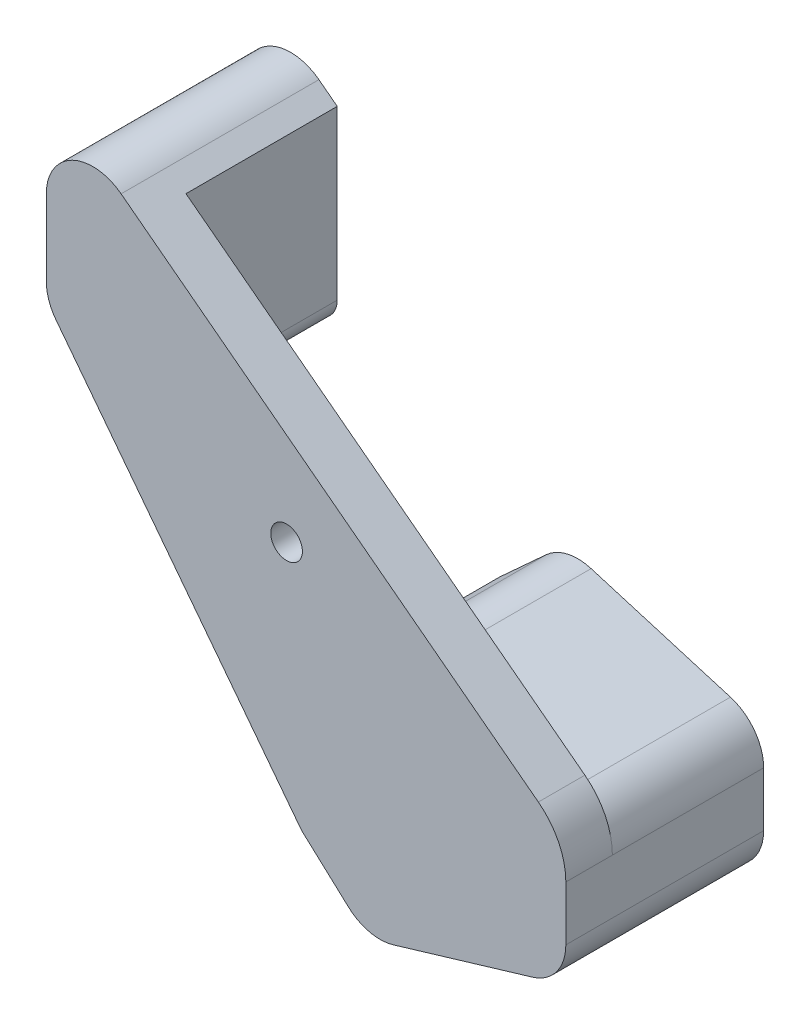
SolidWorks part; units mm, degrees
ref_plane "Front Plane" through (0, 0, 0) normal (0, 0, 1) x (1, 0, 0)
ref_plane "Top Plane" through (0, 0, 0) normal (0, 1, 0) x (1, 0, 0)
ref_plane "Right Plane" through (0, 0, 0) normal (1, 0, 0) x (0, 0, -1)
sketch "Sketch1" plane through (0, 0, 0) normal (0, 0, 1) x (1, 0, 0)
  line L0 (0, 0) -> (0, 12.7)
  line L1 (0, 12.7) -> (11.1125, 22.86)
  line L3 (11.1125, 22.86) -> (38.1, 14.7942)
  line L4 (38.1, 14.7942) -> (38.1, -19.05)
  line L5 (11.1125, 12.7) -> (11.1125, 0) construction
  line L6 (11.1125, 6.35) -> (30.1625, 6.35) construction
  line L7 (11.1125, -10.16) -> (38.1, -2.0942)
  line L8 (0, 0) -> (11.1125, -10.16)
  circle A0 centre (11.1125, 12.7) radius 2.032
  circle A1 centre (11.1125, 0) radius 2.032
  circle A2 centre (30.1625, 6.35) radius 2.032
  dimension "D3" = 4.064
  dimension "D1" = 73.36
  dimension "D2" = 38.1
  dimension "D4" = 11.1125
  dimension "D5" = 12.7
  dimension "D6" = 10.16
  dimension "D7" = 19.05
  dimension "D8" = 19.05
extrude "Boss-Extrude1" add sketch "Sketch1" along normal blind 20.6375 contours L0 L8 L7 L4 L3 L1 A2 A1 A0 region at (18.6064, 6.35, 0)
fillet "Fillet1" radius 6.35 6 edges at (38.1, 14.7942, 10.3187) (11.1125, 22.86, 10.3187) (0, 12.7, 10.3187) (38.1, -2.0942, 10.3187) (11.1125, -10.16, 10.3187) (0, 0, 10.3187)
sketch "Sketch3" plane through (0, 0, 20.6375) normal (0, 0, 1) x (1, 0, 0)
  line L0 (2.0652, -1.8882) -> (-32.7759, 43.4132)
  line L1 (-32.7759, 43.4132) -> (-32.7759, 68.8132)
  line L2 (-32.7759, 68.8132) -> (34.3497, 17.6393)
  line L6 (14.5601, -9.1296) -> (33.5684, -3.4485)
  line L7 (38.1, 2.6355) -> (38.1, 10.0645)
  line L8 (33.5684, 16.1485) -> (14.5601, 21.8296)
  line L9 (8.4569, 20.432) -> (2.0652, 14.5882)
  line L10 (0, 9.9017) -> (0, 2.7983)
  line L11 (2.0652, -1.8882) -> (8.4569, -7.732)
  line L12 (14.5601, -9.1296) -> (33.5684, -3.4485)
  line L13 (38.1, 2.6355) -> (38.1, 10.0645)
  line L17 (2.0652, -1.8882) -> (8.4569, -7.732)
  arc A0 (38.1, 10.0645) -> (34.3497, 17.6393) centre (28.575, 10.0645) ccw
  circle A1 centre (0, 31.1519) radius 2.159 construction
  circle A2 centre (0, 31.1519) radius 2.159
  arc A6 (33.5684, -3.4485) -> (38.1, 2.6355) centre (31.75, 2.6355) ccw
  arc A7 (38.1, 10.0645) -> (33.5684, 16.1485) centre (31.75, 10.0645) ccw
  arc A8 (14.5601, 21.8296) -> (8.4569, 20.432) centre (12.7417, 15.7455) ccw
  arc A9 (2.0652, 14.5882) -> (0, 9.9017) centre (6.35, 9.9017) ccw
  arc A10 (0, 2.7983) -> (2.0652, -1.8882) centre (6.35, 2.7983) ccw
  arc A11 (8.4569, -7.732) -> (14.5601, -9.1296) centre (12.7417, -3.0455) ccw
  arc A12 (33.5684, -3.4485) -> (38.1, 2.6355) centre (31.75, 2.6355) ccw
  arc A17 (8.4569, -7.732) -> (14.5601, -9.1296) centre (12.7417, -3.0455) ccw
  point P12 (34.3204, 17.9923)
  point P20 (-10.7683, 59.9009)
  point P27 (-11.5091, 59.7694)
  point P28 (-11.431, 59.8295)
  point P29 (-30.6124, 77.8528)
  point P30 (-30.6124, 84.739)
  point P31 (-32.7759, 84.3717)
  dimension "D2" = 57.15
  dimension "D3" = 9.525
  dimension "D4" = 170
  dimension "D5" = 25.4
  dimension "D1" = 0
extrude "Boss-Extrude2" add sketch "Sketch3" along normal blind 6.35
fillet "Fillet2" radius 6.35 2 edges at (-32.7759, 43.4132, 23.8125) (-32.7759, 68.8132, 23.8125)
sketch "Sketch4" plane through (0, 0, 20.6375) normal (0, 0, -1) x (-1, 0, 0)
  line L0 (32.7759, 55.9874) -> (32.7759, 45.5727) construction
  line L1 (32.7759, 55.9874) -> (32.7759, 45.5727)
  line L2 (22.5761, 61.0373) -> (20.0759, 59.1312)
  line L3 (-34.3497, 17.6393) -> (22.5761, 61.0373) construction
  line L4 (31.4594, 41.7014) -> (20.0759, 26.9003)
  line L5 (20.0759, 59.1312) -> (20.0759, 26.9003)
  arc A0 (31.4594, 41.7014) -> (32.7759, 45.5727) centre (26.4259, 45.5727) ccw construction
  arc A1 (32.7759, 55.9874) -> (22.5761, 61.0373) centre (26.4259, 55.9874) ccw construction
  arc A2 (31.4594, 41.7014) -> (32.7759, 45.5727) centre (26.4259, 45.5727) ccw
  arc A3 (32.7759, 55.9874) -> (22.5761, 61.0373) centre (26.4259, 55.9874) ccw
  circle A4 centre (26.4259, 55.9874) radius 2.032
  circle A5 centre (26.4259, 45.5727) radius 2.032
  dimension "D2" = 4.064
  dimension "D1" = 12.7
extrude "Boss-Extrude3" add sketch "Sketch4" along normal up to surface (20.6375 mm away)
ref_plane "Plane1" through (0, 0, -2.54) normal (0, 0, -1) x (-1, 0, 0)
fillet "Fillet3" radius 3.175 1 edges at (-20.0759, 26.9003, 10.3188)
mirror "Mirror2" [suppressed] about plane through (0, 0, -2.54) normal (0, 0, -1) of bodies 103
delete or keep bodies "Body-Delete/Keep 1" [suppressed] type delete bodies bodies 103
